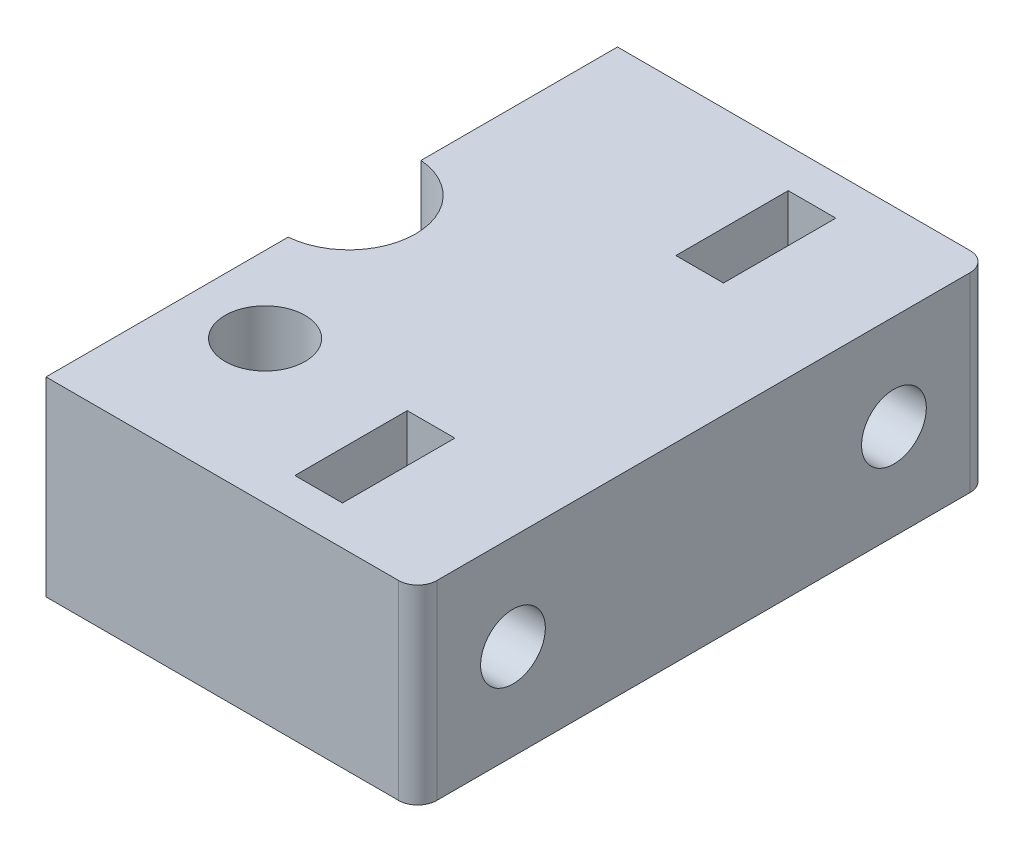
SolidWorks part; units mm, degrees
ref_plane "Front Plane" through (0, 0, 0) normal (0, 0, 1) x (1, 0, 0)
ref_plane "Top Plane" through (0, 0, 0) normal (0, 1, 0) x (1, 0, 0)
ref_plane "Right Plane" through (0, 0, 0) normal (1, 0, 0) x (0, 0, -1)
sketch "Sketch1" plane through (0, 0, 0) normal (0, 1, 0) x (1, 0, 0)
  line L1 (-29.5136, -15) -> (29.5136, -15)
  line L2 (-29.5136, -15) -> (-29.5136, 15)
  line L3 (-29.5136, 15) -> (29.5136, 15)
  line L4 (29.5136, -15) -> (29.5136, 15)
  line L5 (-29.5136, -15) -> (29.5136, 15) construction
  line L6 (-29.5136, 15) -> (29.5136, -15) construction
  point P0 (0, 0)
  dimension "D1" = 59.0272
  dimension "D2" = 30
extrude "Boss-Extrude1" add sketch "Sketch1" along normal blind 10
sketch "Sketch2" plane through (0, 10, 0) normal (0, 1, 0) x (1, 0, 0)
  line L0 (-6, -7.5) -> (14, -7.5) construction
  line L1 (29.5136, -15) -> (29.5136, 15) construction
  line L3 (4, 15) -> (4, -15) construction
  line L5 (-29.5136, -15) -> (29.5136, -15) construction
  circle A0 centre (-6, -7.5) radius 2.1
  circle A1 centre (14, -7.5) radius 2.1
  point P3 (4, -7.5)
  point P5 (0, 0)
  point P12 (0, 0)
  dimension "D1" = 4.2
  dimension "D2" = 20
  dimension "D3" = 7.5
  dimension "D4" = 25.5136
extrude "Cut-Extrude1" cut sketch "Sketch2" against normal through all
sketch "Sketch3" plane through (29.5136, 0, 0) normal (1, 0, 0) x (0, 0, -1)
  line L0 (0, 10) -> (0, 0) construction
  line L1 (-15, 10) -> (15, 10) construction
  line L2 (-15, 0) -> (15, 0) construction
  line L3 (-10, 5) -> (10, 5) construction
  circle A0 centre (-10, 5) radius 1.7
  circle A1 centre (10, 5) radius 1.7
  point P9 (0, 5)
  dimension "D2" = 3.4
  dimension "D1" = 20
extrude "Cut-Extrude2" cut sketch "Sketch3" against normal blind 12
sketch "Sketch4" plane through (-29.5136, 0, 0) normal (-1, 0, 0) x (0, 0, 1)
  line L0 (0, 10) -> (0, 0) construction
  line L3 (-10, 5) -> (10, 5) construction
  line L4 (-15, 10) -> (15, 10) construction
  circle A0 centre (-10, 5) radius 1.65
  circle A1 centre (10, 5) radius 1.65
  point P9 (0, 5)
  dimension "D2" = 3.3
  dimension "D1" = 20
extrude "Cut-Extrude3" cut sketch "Sketch4" against normal blind 12
ref_plane "Plane1" through (23.5136, 0, 0) normal (1, 0, 0) x (0, 0, -1)
ref_plane "Plane2" through (-23.5136, 0, 0) normal (-1, 0, 0) x (0, 0, 1)
sketch "Sketch5" plane through (23.5136, 0, 0) normal (1, 0, 0) x (0, 0, -1)
  line L0 (-12.95, 6.7032) -> (-12.95, 10)
  line L1 (-7.05, 6.7032) -> (-10, 8.4064) construction
  line L2 (-10, 8.4064) -> (-12.95, 6.7032) construction
  line L3 (-12.95, 6.7032) -> (-12.95, 3.2968)
  line L4 (-12.95, 3.2968) -> (-10, 1.5936)
  line L5 (-10, 1.5936) -> (-7.05, 3.2968)
  line L6 (-7.05, 3.2968) -> (-7.05, 6.7032)
  line L7 (10, 8.4064) -> (7.05, 6.7032) construction
  line L8 (7.05, 6.7032) -> (7.05, 3.2968)
  line L9 (7.05, 3.2968) -> (10, 1.5936)
  line L10 (10, 1.5936) -> (12.95, 3.2968)
  line L11 (12.95, 3.2968) -> (12.95, 6.7032)
  line L12 (12.95, 6.7032) -> (10, 8.4064) construction
  line L13 (-15, 10) -> (15, 10) construction
  line L14 (-12.95, 10) -> (-7.05, 10)
  line L15 (-7.05, 10) -> (-7.05, 6.7032)
  line L16 (7.05, 6.7032) -> (7.05, 10)
  line L17 (7.05, 10) -> (12.95, 10)
  line L18 (12.95, 10) -> (12.95, 6.7032)
  circle A0 centre (-10, 5) radius 2.95 construction
  circle A1 centre (10, 5) radius 2.95 construction
  dimension "D1" = 5.9
extrude "Cut-Extrude4" cut sketch "Sketch5" against normal blind 2.5
sketch "Sketch6" plane through (-23.5136, 0, 0) normal (-1, 0, 0) x (0, 0, 1)
  line L0 (-12.85, 6.6454) -> (-12.85, 10)
  line L1 (-7.15, 6.6454) -> (-10, 8.2909) construction
  line L2 (-10, 8.2909) -> (-12.85, 6.6454) construction
  line L3 (-12.85, 6.6454) -> (-12.85, 3.3546)
  line L4 (-12.85, 3.3546) -> (-10, 1.7091)
  line L5 (-10, 1.7091) -> (-7.15, 3.3546)
  line L6 (-7.15, 3.3546) -> (-7.15, 6.6454)
  line L7 (10, 8.2909) -> (7.15, 6.6454) construction
  line L8 (7.15, 6.6454) -> (7.15, 3.3546)
  line L9 (7.15, 3.3546) -> (10, 1.7091)
  line L10 (10, 1.7091) -> (12.85, 3.3546)
  line L11 (12.85, 3.3546) -> (12.85, 6.6454)
  line L12 (12.85, 6.6454) -> (10, 8.2909) construction
  line L14 (-12.85, 10) -> (-7.15, 10)
  line L15 (-7.15, 10) -> (-7.15, 6.6454)
  line L16 (7.15, 6.6454) -> (7.15, 10)
  line L17 (7.15, 10) -> (12.85, 10)
  line L18 (12.85, 10) -> (12.85, 6.6454)
  line L19 (-15, 10) -> (15, 10) construction
  circle A0 centre (-10, 5) radius 2.85 construction
  circle A1 centre (10, 5) radius 2.85 construction
  circle A2 centre (-10, 5) radius 1.65 construction
  circle A3 centre (-10, 5) radius 1.65 construction
  circle A5 centre (10, 5) radius 1.65 construction
  circle A6 centre (10, 5) radius 1.65 construction
  dimension "D1" = 5.7
extrude "Cut-Extrude5" cut sketch "Sketch6" against normal blind 2.3
sketch "Sketch7" plane through (0, 10, 0) normal (0, 1, 0) x (1, 0, 0)
  line L1 (-29.5136, -15) -> (29.5136, -15) construction
  line L2 (9.7, 1.2) -> (-15.7, 1.2) construction
  line L3 (-29.5136, 15) -> (-29.5136, -15) construction
  circle A0 centre (9.7, 1.2) radius 3.5
  circle A1 centre (-15.7, 1.2) radius 3.5
  dimension "D3" = 7
  dimension "D1" = 13.8136
  dimension "D2" = 16.2
  dimension "D4" = 25.4
extrude "Cut-Extrude6" cut sketch "Sketch7" against normal through all
fillet "Fillet1" radius 1 4 edges at (29.5136, 5, -15) (29.5136, 5, 15) (-29.5136, 5, -15) (-29.5136, 5, 15)
sketch "Sketch8" plane through (0, 10, 0) normal (0, 1, 0) x (1, 0, 0)
  line L1 (-29.5136, -15) -> (10, -15)
  line L2 (-28.5136, -15) -> (28.5136, -15) construction
  line L3 (10, -15) -> (10, 15)
  line L4 (-29.5136, -15) -> (-29.5136, 15)
  line L6 (-29.5136, 14) -> (-29.5136, -14) construction
  line L7 (28.5136, 15) -> (-28.5136, 15) construction
  line L8 (10, 15) -> (-29.5136, 15)
  dimension "D1" = 10
extrude "Cut-Extrude7" cut sketch "Sketch8" against normal through all
